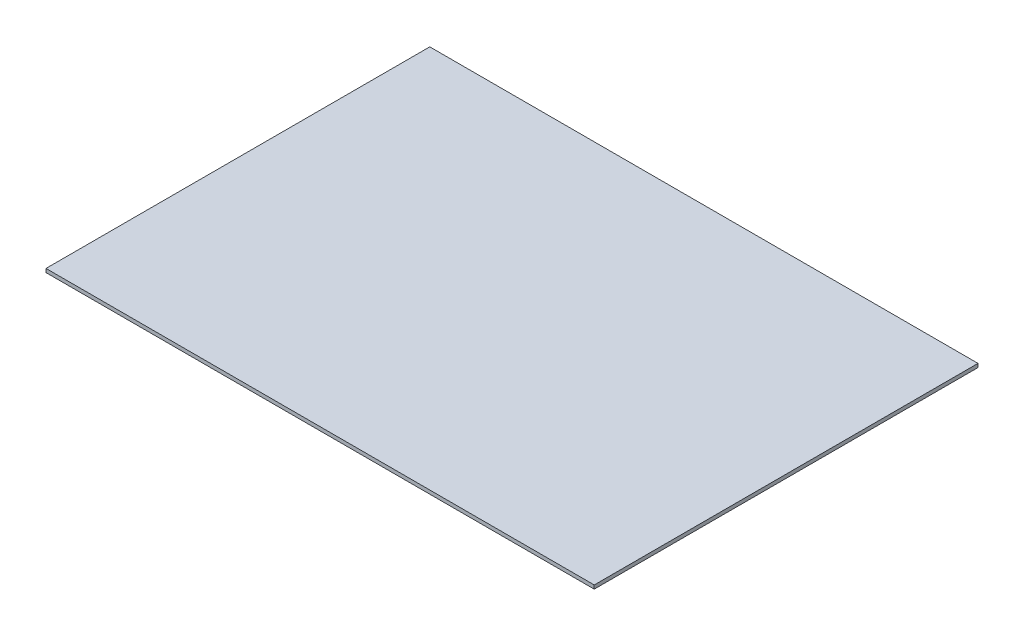
SolidWorks part; units mm, degrees
ref_plane "Front Plane" through (0, 0, 0) normal (0, 0, 1) x (1, 0, 0)
ref_plane "Top Plane" through (0, 0, 0) normal (0, 1, 0) x (1, 0, 0)
ref_plane "Right Plane" through (0, 0, 0) normal (1, 0, 0) x (0, 0, -1)
sketch "Sketch1" plane through (0, 0, 0) normal (0, 1, 0) x (1, 0, 0)
  line L1 (-75, -52.5) -> (75, -52.5)
  line L2 (-75, -52.5) -> (-75, 52.5)
  line L3 (-75, 52.5) -> (75, 52.5)
  line L4 (75, -52.5) -> (75, 52.5)
  line L5 (-75, -52.5) -> (75, 52.5) construction
  line L6 (-75, 52.5) -> (75, -52.5) construction
  point P0 (0, 0)
  dimension "D1" = 105
  dimension "D2" = 150
extrude "Boss-Extrude1" add sketch "Sketch1" against normal blind 1 contours L2 L1 L4 L3
